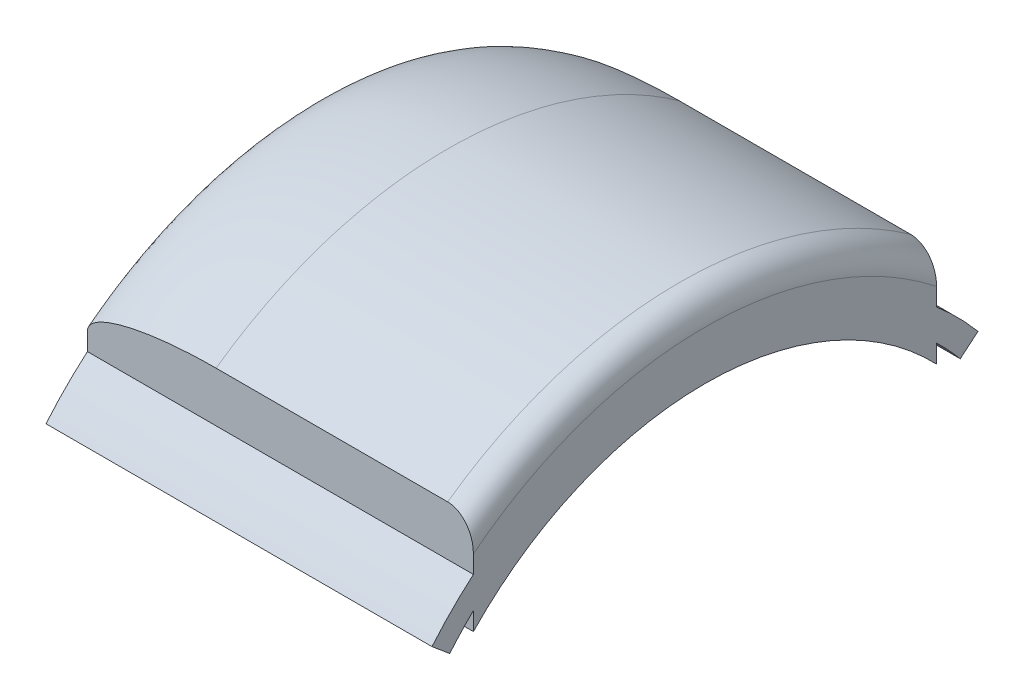
SolidWorks part; units mm, degrees
material "ABS"
ref_plane "Přední rovina" through (0, 0, 0) normal (0, 0, 1) x (1, 0, 0)
ref_plane "Horní rovina" through (0, 0, 0) normal (0, 1, 0) x (1, 0, 0)
ref_plane "Pravá rovina" through (0, 0, 0) normal (1, 0, 0) x (0, 0, -1)
sketch "Skica1" plane through (0, 0, 0) normal (0, 0, 1) x (1, 0, 0)
  line L0 (-22.0025, 0) -> (25.5285, 0) construction
  line L1 (-18.0063, 0) -> (-18.0063, 15.5)
  line L2 (-18.0063, 15.5) -> (8.9937, 15.5)
  line L3 (9.9937, 14.5) -> (9.9937, 12.5)
  line L4 (9.9937, 12.5) -> (-5.0063, 12.5)
  line L5 (-15.0063, 10.5) -> (-15.0063, 0)
  line L6 (-15.0063, 0) -> (-18.0063, 0)
  line L7 (-18.0063, 12.9944) -> (-4.5063, 15.5)
  line L10 (-15.0063, 10.5) -> (-5.0063, 10.5)
  line L11 (-5.0063, 12.5) -> (-5.0063, 10.5)
  line L12 (7.9937, 12.5) -> (9.9937, 12.6048)
  arc A0 (8.9937, 15.5) -> (9.9937, 14.5) centre (8.9937, 14.5) cw
  dimension "D1" = 12.5
  dimension "D2" = 3
  dimension "D3" = 3
  dimension "D8" = 1
  dimension "D4" = 25
  dimension "D5" = 10
  dimension "D6" = 2
  dimension "D7" = 3
  dimension "D9" = 3
  dimension "D10" = 2
revolve "Rotovat1" add sketch "Skica1" angle 360 about L0 region at (-7.4862, 11.1675, 0)
sketch "Skica2" plane through (9.9937, 0, 0) normal (1, 0, 0) x (0, 0, -1)
  line L0 (-9.9203, 8.4741) -> (-10.6097, 9.0526)
  line L1 (-9, 17) -> (9, 17)
  line L2 (-9, 17) -> (-9, 10.6772)
  line L3 (-9, 0.15) -> (9, 0.15)
  line L4 (9, 17) -> (9, 10.6772)
  line L6 (10.6097, 9.0526) -> (9.9203, 8.4741)
  line L7 (-10.6097, 9.0526) -> (0, 0.15) construction
  line L8 (0, 0.15) -> (10.6097, 9.0526) construction
  line L9 (0, 0.15) -> (0, 17) construction
  line L10 (-9, 9.4614) -> (-9, 0.15)
  line L11 (9, 9.4614) -> (9, 0.15)
  arc A0 (-9, 9.4614) -> (-9.9203, 8.4741) centre (0, 0.15) ccw
  arc A1 (10.6097, 9.0526) -> (9, 10.6772) centre (0, 0.15) ccw
  arc A2 (9.9203, 8.4741) -> (9, 9.4614) centre (0, 0.15) ccw
  circle A3 centre (0, 0) radius 14.5 construction
  arc A4 (-9, 10.6772) -> (-10.6097, 9.0526) centre (0, 0.15) ccw
  circle A5 centre (0, 0.15) radius 12.45
  circle A6 centre (0, 0.15) radius 27.7736
  circle A8 centre (0, 0) radius 15.5
  arc A9 (0, 12.65) -> (9, 8.8247) centre (0, 0.15) ccw
  point P4 (0, 17)
  circle M5 centre (0, 0) radius 12.6048
  circle M6 centre (0, 0) radius 14.5
  dimension "D4" = 0.9
  dimension "D5" = 0.5
  dimension "D7" = 25
  dimension "D1" = 0
  dimension "D2" = 18
  dimension "D3" = 50
  dimension "D6" = 50
extrude "Přidat vysunutím2" add sketch "Skica2" along normal blind 15 contours L2 A4 L0 A0 L10 L11 A2 L6 A1 L4 M5 M6 | L4 A8 L2 M6 | L11 A9 L10 A5 M5 region at (9.9937, 8.9323, 10.1232) region at (9.9937, 8.8227, 8.9763) region at (9.9937, 11.9941, 8.8153)
sketch "Skica3" plane through (0, 0, 0) normal (0, 0, 1) x (1, 0, 0)
  line L1 (9.9937, 17.0874) -> (-18.9652, 17.0874)
  line L2 (9.9937, 17.0874) -> (9.9937, -17.2807)
  line L3 (9.9937, -17.2807) -> (-18.9652, -17.2807)
  line L4 (-18.9652, 17.0874) -> (-18.9652, -17.2807)
extrude "Odebrat vysunutím2" cut sketch "Skica3" against normal mid plane 38.9409
fillet "Zaoblit7" radius 1 1 edges at (24.9937, 15.5, 0)
fillet "Zaoblit8" radius 1 1 edges at (9.9937, 15.5, 0) second distance 5 first distance on face at (9.9937, 10.4668, 0)
